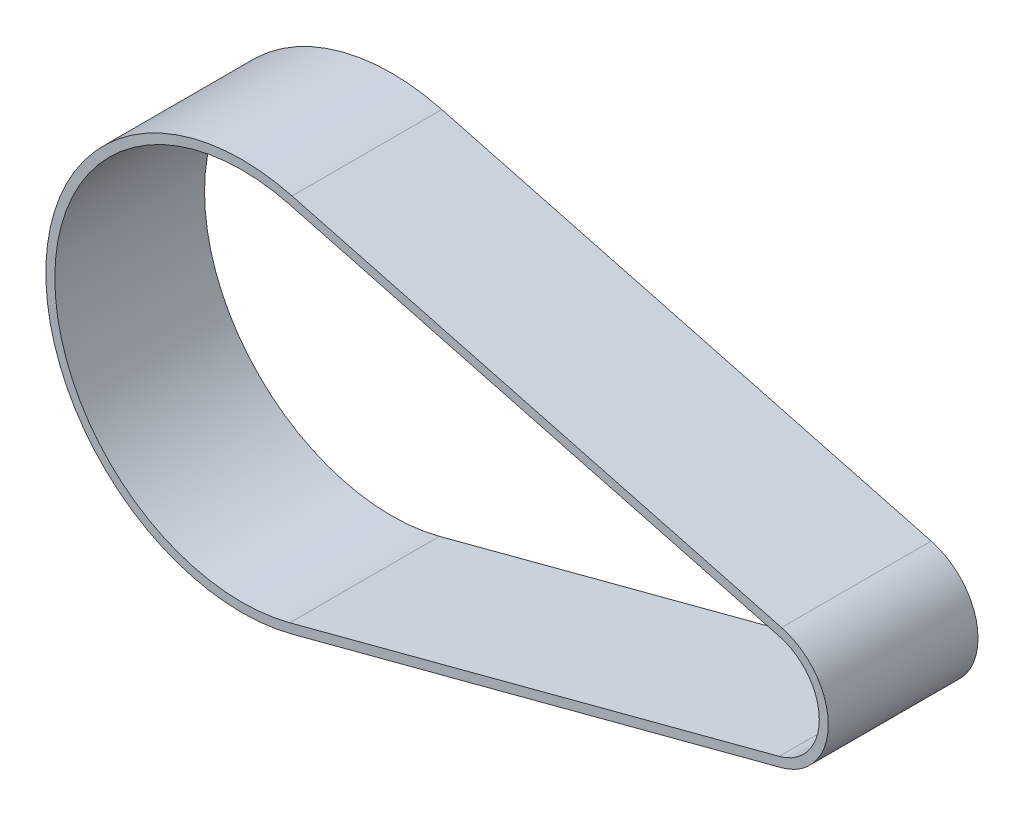
SolidWorks part; units mm, degrees
material "Rubber"
ref_plane "Front Plane" through (0, 0, 0) normal (0, 0, 1) x (1, 0, 0)
ref_plane "Top Plane" through (0, 0, 0) normal (0, 1, 0) x (1, 0, 0)
ref_plane "Right Plane" through (0, 0, 0) normal (1, 0, 0) x (0, 0, -1)
sketch "Sketch1" plane through (0, 0, 0) normal (0, 0, 1) x (1, 0, 0)
  line L0 (13.75, 0) -> (-13.75, 0) construction
  line L1 (-79.4312, 30.2272) -> (2.2892, 8.6833)
  line L2 (-79.4312, -30.2272) -> (2.2892, -8.6833)
  line L3 (-79.0489, 31.6777) -> (2.6716, 10.1338)
  line L4 (-79.0489, -31.6777) -> (2.6716, -10.1338)
  arc A0 (-79.4312, 30.2272) -> (-79.4312, -30.2272) centre (-87.4, 0) ccw
  arc A1 (2.2892, -8.6833) -> (2.2892, 8.6833) centre (0, 0) ccw
  arc A2 (2.6716, -10.1338) -> (2.6716, 10.1338) centre (0, 0) ccw
  arc A3 (-79.0489, 31.6777) -> (-79.0489, -31.6777) centre (-87.4, 0) ccw
  arc A4 (2.2892, -8.6833) -> (2.2892, 8.6833) centre (0, 0) ccw construction
  circle A5 centre (-87.4, 0) radius 34.7298 construction
  arc A6 (-93.4738, 30.6643) -> (-97.2521, 29.6669) centre (-87.4, 0) ccw construction
  arc A7 (8.2209, 3.6135) -> (7.7681, 4.5052) centre (0, 0) ccw construction
  dimension "D1" = 1.5
extrude "Boss-Extrude1" add sketch "Sketch1" along normal blind 25
